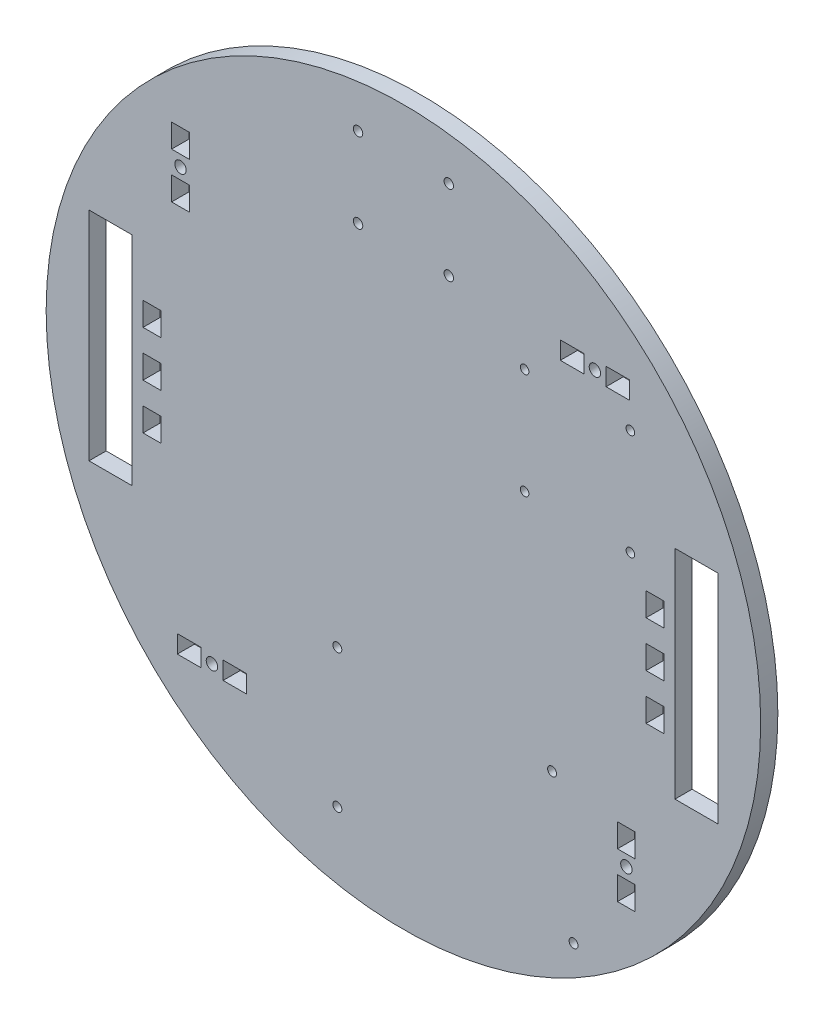
SolidWorks part; units mm, degrees
ref_plane "Plan de face" through (0, 0, 0) normal (0, 0, 1) x (1, 0, 0)
ref_plane "Plan de dessus" through (0, 0, 0) normal (0, 1, 0) x (1, 0, 0)
ref_plane "Plan de droite" through (0, 0, 0) normal (1, 0, 0) x (0, 0, -1)
sketch "Esquisse1" plane through (0, 0, 0) normal (0, 0, 1) x (1, 0, 0)
  line L0 (-125, 0) -> (125, 0) construction
  circle A0 centre (0, 0) radius 125
  dimension "D1" = 250
extrude "Boss.-Extru.1" add sketch "Esquisse1" along normal blind 6
sketch "Esquisse2" plane through (0, 0, 6) normal (0, 0, 1) x (1, 0, 0)
  line L0 (0, 0) -> (-125, 0) construction
  line L1 (-110, 38) -> (-95, 38)
  line L2 (-95, 38) -> (-95, -38)
  line L3 (-110, 38) -> (-110, -38)
  line L4 (-110, -38) -> (-95, -38)
  circle A0 centre (0, 0) radius 125 construction
  dimension "D1" = 38
  dimension "D2" = 38
  dimension "D3" = 15
  dimension "D4" = 95
extrude "Enlèv. mat.-Extru.1" cut sketch "Esquisse2" against normal through all
mirror "Symétrie1" about plane through (0, 0, 0) normal (1, 0, 0) of "Enlèv. mat.-Extru.1"
sketch "Esquisse3" plane through (0, 0, 0) normal (0, 0, -1) x (-1, 0, 0)
  line L0 (-75, 81.1) -> (-75, 74.9) construction
  line L1 (-79.1, 81.1) -> (-70.9, 81.1)
  line L2 (-79.1, 81.1) -> (-79.1, 74.9)
  line L3 (-79.1, 74.9) -> (-70.9, 74.9)
  line L4 (-70.9, 81.1) -> (-70.9, 74.9)
  line L5 (-63.1, 74.9) -> (-54.9, 74.9)
  line L6 (-63.1, 74.9) -> (-63.1, 81.1)
  line L7 (-63.1, 81.1) -> (-54.9, 81.1)
  line L8 (-54.9, 74.9) -> (-54.9, 81.1)
  line L9 (0, 0) -> (0, 69.6176) construction
  line L10 (0, 0) -> (63.3727, 0) construction
  line L11 (-59, 81.1) -> (-59, 74.9) construction
  line L12 (-79.1, 78) -> (-54.9, 78) construction
  circle A0 centre (-67, 78) radius 2
  dimension "D6" = 4
  dimension "D1" = 8.2
  dimension "D2" = 8
  dimension "D3" = 6.2
  dimension "D4" = 8.2
  dimension "D5" = 8
  dimension "D7" = 67
  dimension "D8" = 78
extrude "Enlèv. mat.-Extru.2" cut sketch "Esquisse3" against normal through all
ref_axis "Axe1" through (0, 0, -0.25) along (0, 0, 1)
pattern_circular "Répétition circulaire1" count 4 over 360 about axis through (0, 0, -0.25) along (0, 0, 1) of "Enlèv. mat.-Extru.2"
sketch "Esquisse4" plane through (0, 0, 0) normal (0, 0, -1) x (-1, 0, 0)
  line L0 (-152.6841, 0) -> (161.6648, 0) construction
  line L2 (91.1, 20.1) -> (84.9, 20.1)
  line L3 (91.1, 20.1) -> (91.1, 11.9)
  line L4 (91.1, -20.1) -> (84.9, -20.1)
  line L5 (84.9, 20.1) -> (84.9, 11.9)
  line L6 (84.9, 11.9) -> (91.1, 11.9)
  line L7 (84.9, -4.1) -> (91.1, -4.1)
  line L8 (91.1, 4.1) -> (84.9, 4.1)
  line L9 (84.9, -11.9) -> (91.1, -11.9)
  line L10 (84.9, 4.1) -> (84.9, -4.1)
  line L11 (91.1, 4.1) -> (91.1, -4.1)
  line L12 (84.9, -11.9) -> (84.9, -20.1)
  line L13 (91.1, -11.9) -> (91.1, -20.1)
  line L14 (88, -20.1) -> (88, 20.1) construction
  line L15 (91.1, 16) -> (84.9, 16) construction
  line L16 (91.1, -16) -> (84.9, -16) construction
  line L17 (95, -38) -> (95, 38) construction
  line L18 (91.1, 0) -> (84.9, 0) construction
  dimension "D1" = 7
  dimension "D2" = 6.2
  dimension "D3" = 16
  dimension "D4" = 16
  dimension "D5" = 8.2
  dimension "D6" = 8.2
  dimension "D8" = 8.2
extrude "Enlèv. mat.-Extru.3" cut sketch "Esquisse4" against normal through all
mirror "Symétrie2" about plane through (0, 0, 0) normal (1, 0, 0) of "Enlèv. mat.-Extru.3"
sketch "Esquisse7" plane through (0, 0, 0) normal (0, 0, -1) x (-1, 0, 0)
  circle A0 centre (23.116, -99.3946) radius 1.5621 construction
  circle A1 centre (23.116, -51.0584) radius 1.5621 construction
  circle A2 centre (-52.0172, -51.0584) radius 1.5621 construction
  circle A3 centre (23.116, -99.3946) radius 1.5621
  circle A4 centre (23.116, -51.0584) radius 1.5621
  circle A5 centre (-52.0172, -51.0584) radius 1.5621
  circle A6 centre (-59.5102, -99.3946) radius 1.5621 construction
  circle A7 centre (-59.5102, -99.3946) radius 1.5621
extrude "Enlèv. mat.-Extru.6" cut sketch "Esquisse7" against normal blind 6
sketch "Esquisse8" plane through (0, 0, 0) normal (0, 0, -1) x (-1, 0, 0)
  circle A0 centre (-79.405, 65.9251) radius 1.5 construction
  circle A1 centre (-42.405, 65.9251) radius 1.5 construction
  circle A2 centre (-42.405, 28.9251) radius 1.5 construction
  circle A3 centre (-79.405, 28.9251) radius 1.5 construction
  circle A4 centre (-79.405, 65.9251) radius 1.5
  circle A5 centre (-42.405, 65.9251) radius 1.5
  circle A6 centre (-42.405, 28.9251) radius 1.5
  circle A7 centre (-79.405, 28.9251) radius 1.5
extrude "Enlèv. mat.-Extru.7" cut sketch "Esquisse8" against normal blind 10
sketch "Esquisse9" plane through (0, 0, 6) normal (0, 0, 1) x (1, 0, 0)
  line L0 (0, 0) -> (0, 125) construction
  line L2 (-15.875, 108.97) -> (15.875, 108.97) construction
  line L3 (-15.875, 108.97) -> (-15.875, 81.03) construction
  line L4 (-15.875, 81.03) -> (15.875, 81.03) construction
  line L5 (15.875, 108.97) -> (15.875, 81.03) construction
  line L6 (-15.875, 108.97) -> (15.875, 81.03) construction
  line L7 (-15.875, 81.03) -> (15.875, 108.97) construction
  circle A0 centre (0, 0) radius 125 construction
  circle A1 centre (-15.875, 108.97) radius 1.65
  circle A2 centre (15.875, 108.97) radius 1.65
  circle A3 centre (15.875, 81.03) radius 1.65
  circle A4 centre (-15.875, 81.03) radius 1.65
  point P5 (0, 95)
  dimension "D3" = 3.3
  dimension "D4" = 3.3
  dimension "D5" = 3.3
  dimension "D6" = 3.3
  dimension "D1" = 31.75
  dimension "D2" = 27.94
  dimension "D7" = 30
extrude "Enlèv. mat.-Extru.8" cut sketch "Esquisse9" against normal up to next
equation "\"D2@Esquisse2\"=\"D1@Esquisse2\""
